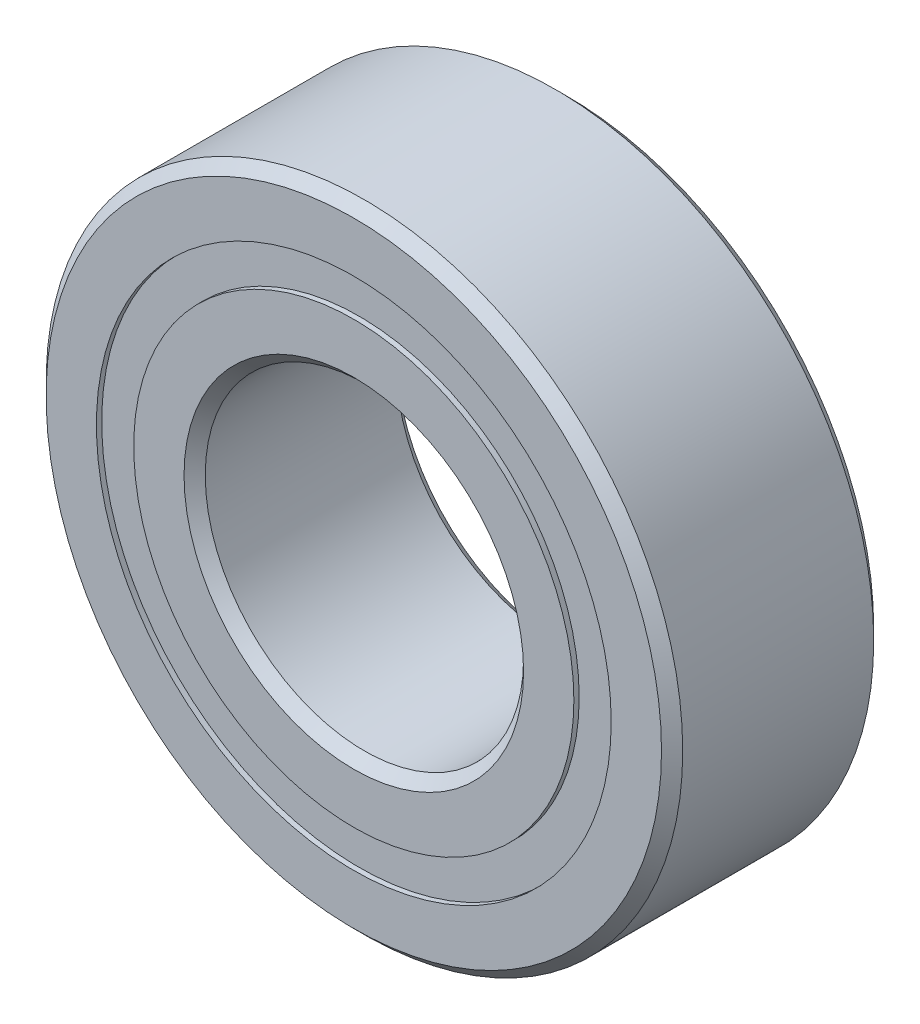
SolidWorks part; units mm, degrees
ref_plane "Front Plane" through (0, 0, 0) normal (0, 0, 1) x (1, 0, 0)
ref_plane "Top Plane" through (0, 0, 0) normal (0, 1, 0) x (1, 0, 0)
ref_plane "Right Plane" through (0, 0, 0) normal (1, 0, 0) x (0, 0, -1)
sketch "Sketch1" plane through (0, 0, 0) normal (1, 0, 0) x (0, 0, -1)
  line L0 (-2, 0) -> (2, 0) construction
  line L1 (0, 6) -> (0, -6) construction
  line L2 (1.8, 6) -> (-1.8, 6)
  line L3 (-1.8, 6) -> (-2, 5.8)
  line L4 (-2, 5.8) -> (-2, 4.8516)
  line L5 (-2, 4.8516) -> (-0.8889, 4.8516)
  line L6 (2, 4.8516) -> (0.8889, 4.8516)
  line L7 (2, 5.8) -> (2, 4.8516)
  line L8 (1.8, 6) -> (2, 5.8)
  line L9 (0, 6) -> (0, 4.5) construction
  line L10 (0, 4.5) -> (0, 3) construction
  arc A0 (-0.8889, 4.8516) -> (0.8889, 4.8516) centre (0, 4.5) cw
  point P14 (0, 3)
  dimension "Width" = 4
  dimension "OD" = 12
  dimension "D1" = 45
  dimension "D2" = 0.2
  dimension "Shaft Dia" = 6
  dimension "D3" = 1.7778
  dimension "D4" = 0.3516
revolve "Revolve1" add sketch "Sketch1" angle 360 about L0
sketch "Sketch3" plane through (0, 0, 0) normal (1, 0, 0) x (0, 0, -1)
  line L0 (-2, 4.1484) -> (-0.8889, 4.1484)
  line L1 (0, 6) -> (0, -6) construction
  line L2 (-2, 5.8) -> (-2, 4.8516) construction
  line L3 (-2, 4.1484) -> (-2, 3.2)
  line L4 (-1.8, 6) -> (-2, 5.8) construction
  line L5 (-2, 3.2) -> (-1.8, 3)
  line L6 (-1.8, 3) -> (1.8, 3)
  line L7 (1.8, 6) -> (1.8, -6) construction
  line L8 (1.8, 3) -> (2, 3.2)
  line L9 (2, -5.8) -> (2, 5.8) construction
  line L10 (2, 3.2) -> (2, 4.1484)
  line L11 (2, 4.1484) -> (0.8889, 4.1484)
  line L13 (1.8, 6) -> (2, 5.8) construction
  arc A0 (0.8889, 4.8516) -> (-0.8889, 4.8516) centre (0, 4.5) ccw construction
  arc A1 (0.8889, 4.1484) -> (-0.8889, 4.1484) centre (0, 4.5) cw
revolve "Revolve3" add sketch "Sketch3" angle 360 about L0
sketch "Sketch4" plane through (0, 0, 0) normal (1, 0, 0) x (0, 0, -1)
  line L0 (-0.9559, 4.5) -> (0.9559, 4.5)
  arc A2 (-0.9559, 4.5) -> (0.9559, 4.5) centre (0, 4.5) cw
  arc A3 (0.8889, 4.8516) -> (-0.8889, 4.8516) centre (0, 4.5) ccw construction
revolve "Revolve4" add sketch "Sketch4" angle 360 about L0
ref_axis "Axis1" through (0, 0, -2) along (0, 0, 1)
pattern_circular "CirPattern1" count 12 every 30 about axis through (0, 0, -2) along (0, 0, 1) of bodies 104
sketch "Sketch5" plane through (0, 0, 0) normal (1, 0, 0) x (0, 0, -1)
  line L0 (-2, 4.8516) -> (-0.8889, 4.8516) construction
  line L1 (-1.9, 4.8516) -> (-0.9559, 4.8516)
  line L2 (-1.9, 4.8516) -> (-1.9, 4.1484)
  line L3 (-1.9, 4.1484) -> (-0.9559, 4.1484)
  line L4 (-0.9559, 4.8516) -> (-0.9559, 4.1484)
  line L5 (-2, 4.1484) -> (-0.8889, 4.1484) construction
  line L6 (2, 4.8516) -> (0.8889, 4.8516) construction
  line L7 (1.9, 4.8516) -> (0.9559, 4.8516)
  line L8 (1.9, 4.8516) -> (1.9, 4.1484)
  line L9 (1.9, 4.1484) -> (0.9559, 4.1484)
  line L10 (0.9559, 4.8516) -> (0.9559, 4.1484)
  line L11 (2, 4.1484) -> (0.8889, 4.1484) construction
  line L12 (-1.8, 6) -> (-2, 5.8) construction
  point P18 (-1.9, 5.9)
revolve "Revolve5" add sketch "Sketch5" angle 360 about L0
sketch "Sketch6" plane through (0, 0, 0) normal (1, 0, 0) x (0, 0, -1)
  line L0 (2, 0) -> (-2, 0) construction
  line L1 (2, 4.8516) -> (0.9, 4.8516)
  line L2 (2, 4.8516) -> (2, 9.5)
  line L3 (2, 9.5) -> (0.9, 9.5)
  line L4 (0.9, 4.8516) -> (0.9, 9.5)
  dimension "Th" = 1.1
  dimension "Flange OD" = 19
revolve "Revolve6" [suppressed] add sketch "Sketch6" angle 360 about L0
equation "\"D2@Sketch1\" = \"Width@Sketch1\"*.05"
equation "\"D3@Sketch1\" = \"Width@Sketch1\"/2.25"
equation "\"D4@Sketch1\" = (((\"OD@Sketch1\"-\"Width@Sketch1\")/2)/3.25)/3.5"
equation "\"D2@CirPattern1\" = 360/\"Balls@CirPattern1\""
